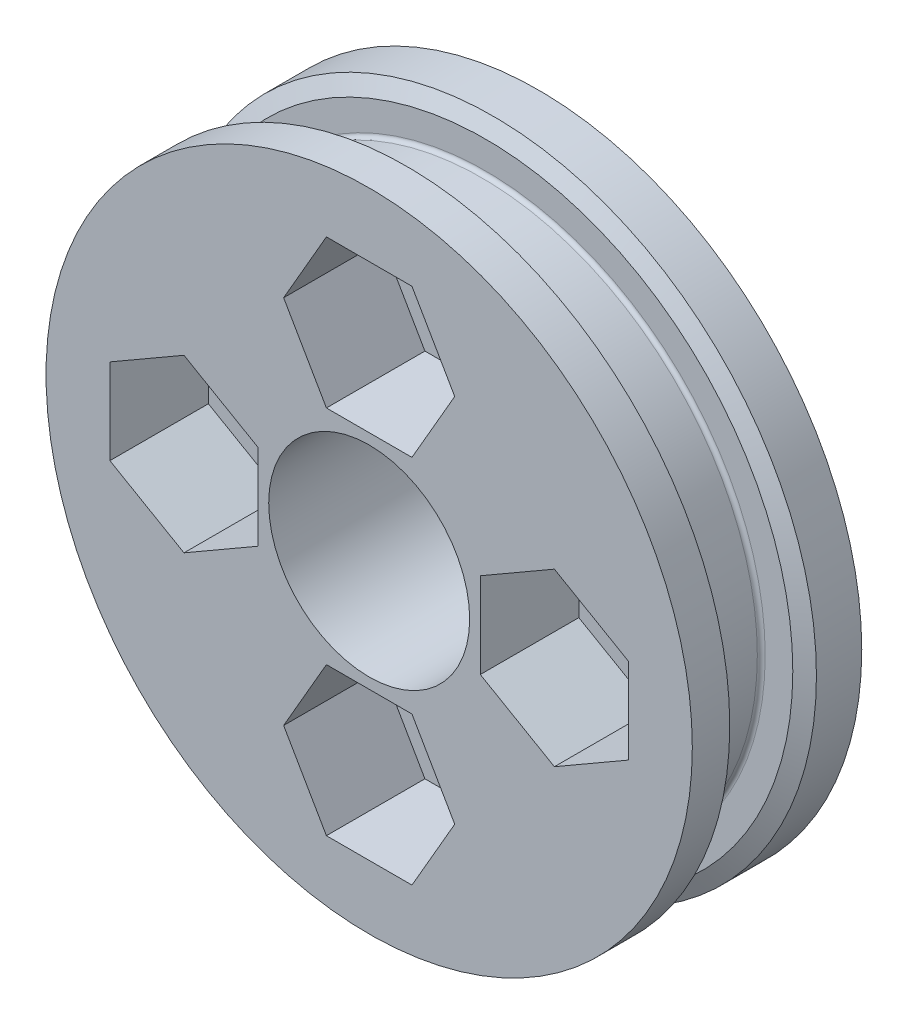
SolidWorks part; units mm, degrees
ref_plane "Front Plane" through (0, 0, 0) normal (0, 0, 1) x (1, 0, 0)
ref_plane "Top Plane" through (0, 0, 0) normal (0, 1, 0) x (1, 0, 0)
ref_plane "Right Plane" through (0, 0, 0) normal (1, 0, 0) x (0, 0, -1)
sketch "Sketch2" plane through (0, 0, 0) normal (1, 0, 0) x (0, 0, -1)
  line L0 (0, 6.477) -> (0, 20.828)
  line L1 (0, 20.828) -> (2.413, 20.828)
  line L2 (2.921, 19.812) -> (2.921, 17.78)
  line L3 (2.921, 17.78) -> (7.493, 17.78)
  line L4 (7.493, 17.78) -> (7.493, 19.812)
  line L5 (8.001, 20.828) -> (10.922, 20.828)
  line L6 (10.922, 20.828) -> (10.922, 6.477)
  line L8 (0, 6.477) -> (10.922, 6.477)
  line L9 (0, 6.477) -> (0, 0) construction
  line L10 (0, 0) -> (10.7816, 0) construction
  line L11 (7.493, 19.812) -> (8.001, 20.828)
  line L12 (2.413, 20.828) -> (2.921, 19.812)
  point P4 (2.921, 20.828)
  point P7 (7.493, 20.828)
  dimension "D1" = 17.78
  dimension "D2" = 10.922
  dimension "D3" = 3.048
  dimension "D4" = 6.477
  dimension "D5" = 4.572
  dimension "D6" = 1.016
  dimension "D7" = 0.508
  dimension "D8" = 0.508
  dimension "D9" = 1.016
  dimension "D10" = 2.921
revolve "Revolve1" add sketch "Sketch2" angle 360 about L10
sketch "Sketch3" plane through (0, 0, -10.922) normal (0, 0, -1) x (-1, 0, 0)
  line L1 (-8.255, -8.255) -> (8.255, -8.255)
  line L2 (-8.255, -8.255) -> (-8.255, 8.255)
  line L3 (-8.255, 8.255) -> (8.255, 8.255)
  line L4 (8.255, -8.255) -> (8.255, 8.255)
  circle A0 centre (0, 0) radius 6.477 construction
  circle A1 centre (0, 0) radius 6.477
  point P4 (8.255, 0)
  point P6 (0, 8.255)
  dimension "D1" = 16.51
extrude "Boss-Extrude1" add sketch "Sketch3" along normal blind 3.175
ref_plane "Plane1" through (0, 0, -5.461) normal (0, 0, -1) x (-1, 0, 0)
sketch "Sketch4" plane through (0, 0, -10.922) normal (0, 0, -1) x (-1, 0, 0)
  line L0 (0, 11.938) -> (0, 0) construction
  line L1 (0, 0) -> (0, -11.938) construction
  line L2 (-11.938, 0) -> (0, 0) construction
  line L3 (0, 0) -> (11.938, 0) construction
  circle A0 centre (0, 11.938) radius 2.54
  circle A1 centre (11.938, 0) radius 2.54
  circle A2 centre (0, -11.938) radius 2.54
  circle A3 centre (-11.938, 0) radius 2.54
  dimension "D1" = 5.08
  dimension "D2" = 11.938
extrude "Cut-Extrude1" cut sketch "Sketch4" against normal through all both and the other way through all
fillet "Fillet1" radius 0.254 2 edges at (17.78, 0, -7.493) (17.78, 0, -2.921)
sketch "Sketch5" plane through (0, 0, 0) normal (0, 0, 1) x (1, 0, 0)
  line L1 (2.757, 7.1628) -> (5.5139, 11.938)
  line L2 (5.5139, 11.938) -> (2.757, 16.7132)
  line L3 (2.757, 16.7132) -> (-2.757, 16.7132)
  line L4 (-2.757, 16.7132) -> (-5.5139, 11.938)
  line L5 (-5.5139, 11.938) -> (-2.757, 7.1628)
  line L6 (-2.757, 7.1628) -> (2.757, 7.1628)
  circle A0 centre (0, 11.938) radius 4.7752 construction
  circle A1 centre (0, 11.938) radius 2.54 construction
  point P1 (0, 0)
  point P11 (5.5139, 11.938)
  dimension "D1" = 9.5504
extrude "Cut-Extrude2" cut sketch "Sketch5" against normal blind 6.35
pattern_circular "CirPattern1" count 4 over 360 about axis through (0, 0, 0) along (0, 0, 1) of "Cut-Extrude2"
